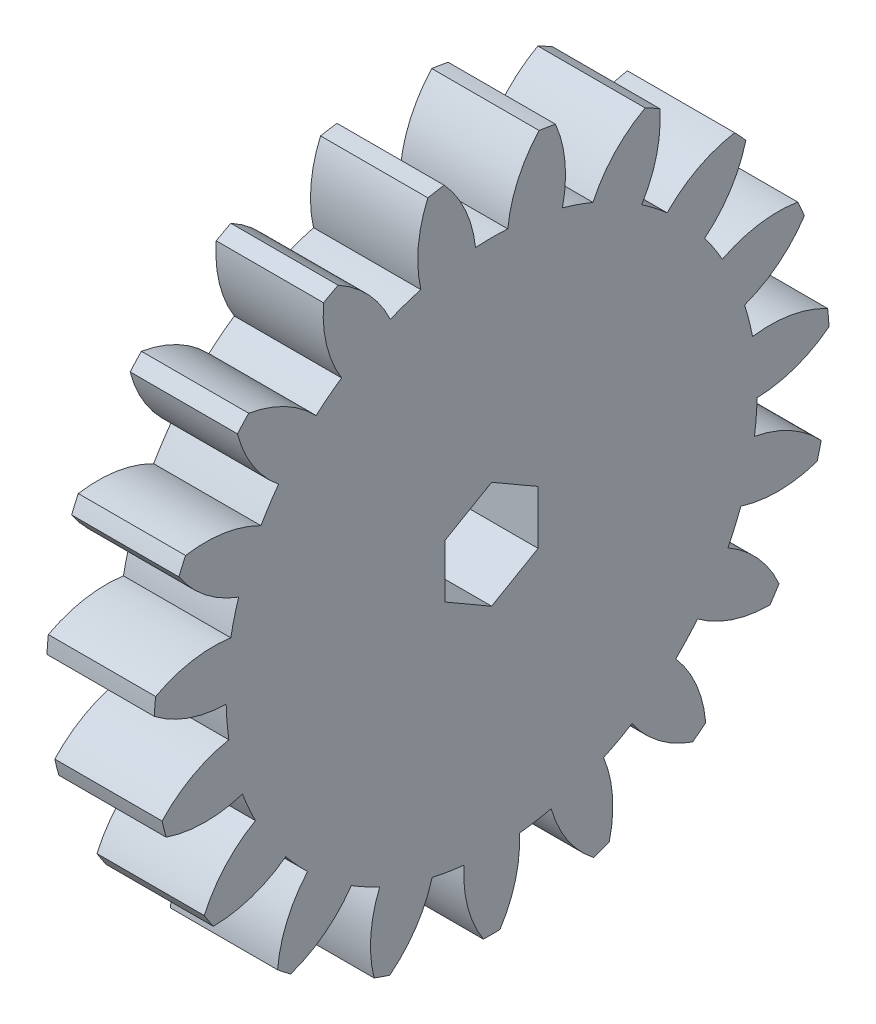
SolidWorks part; units mm, degrees
ref_plane "Plane1" through (0, 0, 0) normal (0, 0, 1) x (1, 0, 0)
ref_plane "Plane2" through (0, 0, 0) normal (0, 1, 0) x (1, 0, 0)
ref_plane "Plane3" through (0, 0, 0) normal (1, 0, 0) x (0, 0, -1)
sketch "HoldingSke" plane through (0, 0, 0) normal (0, 1, 0) x (1, 0, 0)
  line L0 (0, 0) -> (0.6303, -0.217)
  line L1 (-15, 0) -> (100, 0) construction
  line L2 (0, 0) -> (-2.1039, 2.3779)
  line L3 (0, 0) -> (-11.863, 4.5341)
  line L4 (0, 0) -> (8.1655, 2.8116)
  line L5 (0, 0) -> (-46.8476, -17.4728)
  line L6 (0, 0) -> (-4.1448, -2.7965)
  line L7 (-2.1039, 2.3779) -> (8.6586, 51.2059)
  line L8 (-76.2, 54.61) -> (-75.3, 54.61)
  line L9 (-71.009, 38.7566) -> (-53.1078, 45.2721)
  line L10 (-76.2, 71.12) -> (104.1128, 71.12)
  line L11 (0, 0) -> (-5, 0)
  line L12 (-76.2, 101.6) -> (-76.147, 101.6)
  line L13 (24.9733, 27.94) -> (52.9518, 28.4284)
  line L14 (24.9733, 27.94) -> (24.9743, 27.94)
  line L15 (24.9733, 27.94) -> (100.4006, 29.5858)
  line L16 (-63.627, -1.5) -> (-12.827, -1.5)
  circle A0 centre (0, 0) radius 2.5
  circle A1 centre (0, 0) radius 12.374
  circle A2 centre (0, 0) radius 37.5
  circle A3 centre (0, 0) radius 2.5
  dimension "MHD" = 24.748
  dimension "Hub_dia" = 75
  dimension "Bore" = 5
  dimension "MBD" = 5
  dimension "Num_teeth" = 19
  dimension "Pitch" = 0.6667
  dimension "Overall_len" = 50
  dimension "Show_teeth" = 19
  dimension "Thickness" = 5
  dimension "OAL" = 50.0001
  dimension "T_dim" = 0.9
  dimension "Ap" = 20
  dimension "H" = 19.05
  dimension "Pitch_radius" = 180.3128
  dimension "Width" = 5
  dimension "Backlash" = 0.053
  dimension "Addendum_fac" = 1
  dimension "Dedendum_fac" = 1.25
  dimension "Clearance_fac" = 0.25
  dimension "Dedendum_add" = 0.001
  dimension "Module" = 1.5
sketch "BasProSke" plane through (0, 0, 0) normal (0, 1, 0) x (1, 0, 0)
  line L0 (-10, 0) -> (60, 0) construction
  line L1 (0, 0) -> (0, 15.75)
  line L2 (0, 0) -> (5, 0)
  line L3 (5, 0) -> (5, 15.75)
  line L4 (5, 15.75) -> (0, 15.75)
  dimension "Thickness" = 5
  dimension "Diameter" = 31.5
revolve "Base-Revolve" add sketch "BasProSke" angle 360 about L0
sketch "TooCutSke" plane through (0, 0, 0) normal (1, 0, 0) x (0, 0, -1)
  line L1 (0, 0) -> (0, 107) construction
  line L2 (0, 0) -> (-1.2695, 14.1933) construction
  line L3 (0, 0) -> (-4.6774, 28.0298) construction
  line L4 (-1.2695, 14.1933) -> (-2.3387, 14.0149) construction
  arc A0 (0.7515, 12.3512) -> (-0.7515, 12.3512) centre (0, 0) ccw
  arc A1 (2.2309, 15.6169) -> (-2.2309, 15.6169) centre (0, 0) ccw
  circle A2 centre (0, 0) radius 14.25 construction
  circle A3 centre (0, 0) radius 13.3906 construction
  arc A4 (-0.7515, 12.3512) -> (-2.2309, 15.6169) centre (-6.4199, 11.7513) ccw
  arc A5 (2.2309, 15.6169) -> (0.7515, 12.3512) centre (6.4199, 11.7513) ccw
  dimension "Root_dia" = 24.748
  dimension "Overcut_dia" = 31.5508
  dimension "Pitch_dia" = 28.5
  dimension "Base_dia" = 26.7812
  dimension "Flank_rad" = 5.7
  dimension "Half_ang" = 9.474
  dimension "Half_CT" = 1.084
extrude "ToothCut" cut sketch "TooCutSke" along normal through all
fillet "Breaks" [suppressed] radius 0.03 tangent propagation no
fillet "RootFillets" [suppressed] radius 0.376
pattern_circular "TeethCuts" count 19 every 18.947 about axis through (-10, 0, 0) along (1, 0, 0) of "ToothCut", "RootFillets", "Breaks"
sketch "HubNeaOneSke" plane through (0, 0, 0) normal (-1, 0, 0) x (0, 0, 1)
  circle A0 centre (0, 0) radius 12.374
  dimension "Diameter" = 24.748
extrude "HubNearOne" [suppressed] add sketch "HubNeaOneSke" along normal blind 45.0001
sketch "HubNeaBotSke" plane through (0, 0, 0) normal (-1, 0, 0) x (0, 0, 1)
  circle A0 centre (0, 0) radius 12.374
  dimension "Diameter" = 24.748
extrude "HubNearBoth" [suppressed] add sketch "HubNeaBotSke" along normal blind 22.5
ref_plane "FarPln" through (5, 0, 0) normal (1, 0, 0) x (0, 0, -1)
sketch "HubFarSke" plane through (5, 0, 0) normal (1, 0, 0) x (0, 0, -1)
  circle A0 centre (0, 0) radius 12.374
  dimension "Diameter" = 24.748
extrude "HubFar" [suppressed] add sketch "HubFarSke" along normal blind 22.5
sketch "BorSke" plane through (0, 0, 0) normal (1, 0, 0) x (0, 0, -1)
  line L1 (0, 2.5) -> (-2.1651, 1.25)
  line L2 (-2.1651, 1.25) -> (-2.1651, -1.25)
  line L3 (-2.1651, -1.25) -> (0, -2.5)
  line L4 (0, -2.5) -> (2.1651, -1.25)
  line L5 (2.1651, -1.25) -> (2.1651, 1.25)
  line L6 (2.1651, 1.25) -> (0, 2.5)
  circle A0 centre (0, 0) radius 2.5 construction
  circle A1 centre (0, 0) radius 2.1651 construction
  point P2 (0, 2.5)
  dimension "Diameter" = 5
extrude "Bore" cut sketch "BorSke" along normal mid plane 100.0001
sketch "KeySke" plane through (0, 0, 0) normal (1, 0, 0) x (0, 0, -1)
  line L0 (-1, 0) -> (-1, 3.4)
  line L1 (-1, 3.4) -> (1, 3.4)
  line L2 (1, 3.4) -> (1, 0)
  line L3 (0, 0) -> (0, 34) construction
  line L4 (-1, 0) -> (1, 0)
  dimension "Offset" = 3.4
  dimension "Width" = 2
extrude "Keyway" [suppressed] cut sketch "KeySke" along normal mid plane 100.0001
pattern_circular "Keyway2" [suppressed] count 2 every 90 about axis through (-10, 0, 0) along (1, 0, 0) reverse direction yes
equation "' \"Module@HoldingSke\" = 6.35"
equation "' \"Num_teeth@HoldingSke\" = 12"
equation "' \"Ap@HoldingSke\" =  20"
equation "' \"Ap@HoldingSke\" = 20"
equation "' \"Width@HoldingSke\" = 0.5 * 25.4"
equation "' \"Hub_dia@HoldingSke\"= 1 * 25.4"
equation "' \"Hub_dia@HoldingSke\" = 1 * 25.4"
equation "' \"Overall_len@HoldingSke\" = 1.0 * 25.4"
equation "' \"Bore@HoldingSke\" = 0.75 * 25.4"
equation "' \"T_dim@HoldingSke\" = 0.1 * 25.4"
equation "' \"Width@KeySke\" = 0.25 * 25.4"
equation "' \"Show_teeth@HoldingSke\" = 13"
equation "' \"Backlash@HoldingSke\" = 0.009 * 25.4"
equation "' \"Addendum_fac@HoldingSke\" = 1.0"
equation "' \"Dedendum_fac@HoldingSke\" = 1.25"
equation "' \"Dedendum_add@HoldingSke\" = 0.00005 * 25.4"
equation "' \"Clearance_fac@HoldingSke\" = 0.25"
equation "\"Pitch@HoldingSke\" = 1 / \"Module@HoldingSke\""
equation "\"Overcut_dia@TooCutSke\" = (\"Num_teeth@HoldingSke\" + 2 * \"Addendum_fac@HoldingSke\") / \"Pitch@HoldingSke\" + 0.002 * 25.4"
equation "\"Pitch_dia@TooCutSke\" = \"Num_teeth@HoldingSke\" / \"Pitch@HoldingSke\""
equation "\"Base_dia@TooCutSke\" = \"Num_teeth@HoldingSke\" / \"Pitch@HoldingSke\" * cos((\"Ap@HoldingSke\"  * 3.14159265 / 180))"
equation "\"Root_dia@TooCutSke\" = (\"Num_teeth@HoldingSke\" + 2) / \"Pitch@HoldingSke\" - 2 * (\"Addendum_fac@HoldingSke\" + \"Dedendum_fac@HoldingSke\") / \"Pitch@HoldingSke\" - \"Dedendum_add@HoldingSke\" * 2"
equation "\"Half_ang@TooCutSke\" = 180 / \"Num_teeth@HoldingSke\""
equation "\"Half_CT@TooCutSke\" = \"Num_teeth@HoldingSke\" / \"Pitch@HoldingSke\" * sin((3.14159265 / 2 / \"Num_teeth@HoldingSke\")) / 2 - 7 * \"Backlash@HoldingSke\" / 4"
equation "\"Flank_rad@TooCutSke\" = \"Num_teeth@HoldingSke\" / \"Pitch@HoldingSke\" / 5"
equation "\"Radius@RootFillets\" = \"Clearance_fac@HoldingSke\" / \"Pitch@HoldingSke\" + \"Dedendum_add@HoldingSke\""
equation "\"Break_rad@Breaks\" = 0.02 / \"Pitch@HoldingSke\""
equation "\"Thickness@HoldingSke\" = \"Width@HoldingSke\""
equation "\"OAL@HoldingSke\" = \"Thickness@HoldingSke\""
equation "\"MHD@HoldingSke\" = (\"Num_teeth@HoldingSke\" + 2) / \"Pitch@HoldingSke\" - 2 * (\"Addendum_fac@HoldingSke\" + \"Dedendum_fac@HoldingSke\")  / \"Pitch@HoldingSke\" - \"Dedendum_add@HoldingSke\" * 2"
equation "\"MBD@HoldingSke\" = (\"Num_teeth@HoldingSke\" + 2) / \"Pitch@HoldingSke\" - 2 * (\"Addendum_fac@HoldingSke\" + \"Dedendum_fac@HoldingSke\")  / \"Pitch@HoldingSke\" - \"Dedendum_add@HoldingSke\" * 2 - 0.002 * 25.4"
equation "\"MHD@HoldingSke\" = ((sgn( \"MHD@HoldingSke\" - \"Hub_dia@HoldingSke\" )-1)*( \"MHD@HoldingSke\" - \"Hub_dia@HoldingSke\" ))/-2+ \"Hub_dia@HoldingSke\""
equation "\"MBD@HoldingSke\" = ((sgn( \"MBD@HoldingSke\" - \"Bore@HoldingSke\" )-1)*( \"MBD@HoldingSke\" - \"Bore@HoldingSke\" ))/-2+ \"Bore@HoldingSke\""
equation "\"OAL@HoldingSke\" = ((sgn( \"OAL@HoldingSke\" - \"Overall_len@HoldingSke\" )+1)*( \"OAL@HoldingSke\" - \"Overall_len@HoldingSke\" ))/2 + \"Overall_len@HoldingSke\" + 0.000002 * 25.4"
equation "\"Num_teeth@TeethCuts\" = int( \"Show_teeth@HoldingSke\" ) + 1"
equation "\"Num_teeth@TeethCuts\" = ((sgn( \"Num_teeth@TeethCuts\" - \"Num_teeth@HoldingSke\" )-1)*( \"Num_teeth@TeethCuts\" - \"Num_teeth@HoldingSke\" ))/-2+ \"Num_teeth@HoldingSke\""
equation "\"Num_teeth@TeethCuts\" = ((sgn( \"Num_teeth@TeethCuts\" - 2.0)+1)*( \"Num_teeth@TeethCuts\" - 2.0))/2 +2.0"
equation "\"Angle@TeethCuts\" = 360.0 / \"Num_teeth@HoldingSke\""
equation "\"Diameter@BasProSke\" = (\"Num_teeth@HoldingSke\" + 2 * \"Addendum_fac@HoldingSke\") / \"Pitch@HoldingSke\""
equation "\"Thickness@BasProSke\"  = \"Thickness@HoldingSke\""
equation "' \"Fillet_rad@BasProSke\" =  \"Thickness@HoldingSke\" * 0.05"
equation "' \"Fillet_rad@BasProSke\" = \"Thickness@HoldingSke\" * 0.05"
equation "\"MHD@HoldingSke\" = ((sgn( \"MHD@HoldingSke\" - \"Root_dia@TooCutSke\" )-1)*( \"MHD@HoldingSke\" - \"Root_dia@TooCutSke\" ))/-2+ \"Root_dia@TooCutSke\""
equation "\"Diameter@HubNeaOneSke\" = \"MHD@HoldingSke\""
equation "\"Length@HubNearOne\" = \"OAL@HoldingSke\" - \"Thickness@BasProSke\""
equation "\"Diameter@HubNeaBotSke\" = \"MHD@HoldingSke\""
equation "\"Length@HubNearBoth\" = ( \"OAL@HoldingSke\" - \"Thickness@BasProSke\" ) / 2.0"
equation "\"Thickness@FarPln\" = \"Thickness@BasProSke\""
equation "\"Diameter@HubFarSke\" = \"MHD@HoldingSke\""
equation "\"Length@HubFar\" = ( \"OAL@HoldingSke\" - \"Thickness@BasProSke\" ) / 2.0"
equation "\"Diameter@BorSke\" = \"MBD@HoldingSke\""
equation "\"D1@Bore\" = \"OAL@HoldingSke\" * 2.0"
equation "\"D1@Keyway\" = \"OAL@HoldingSke\" * 2.0"
equation "\"Offset@KeySke\" = \"T_dim@HoldingSke\" + \"MBD@HoldingSke\" / 2.0"
